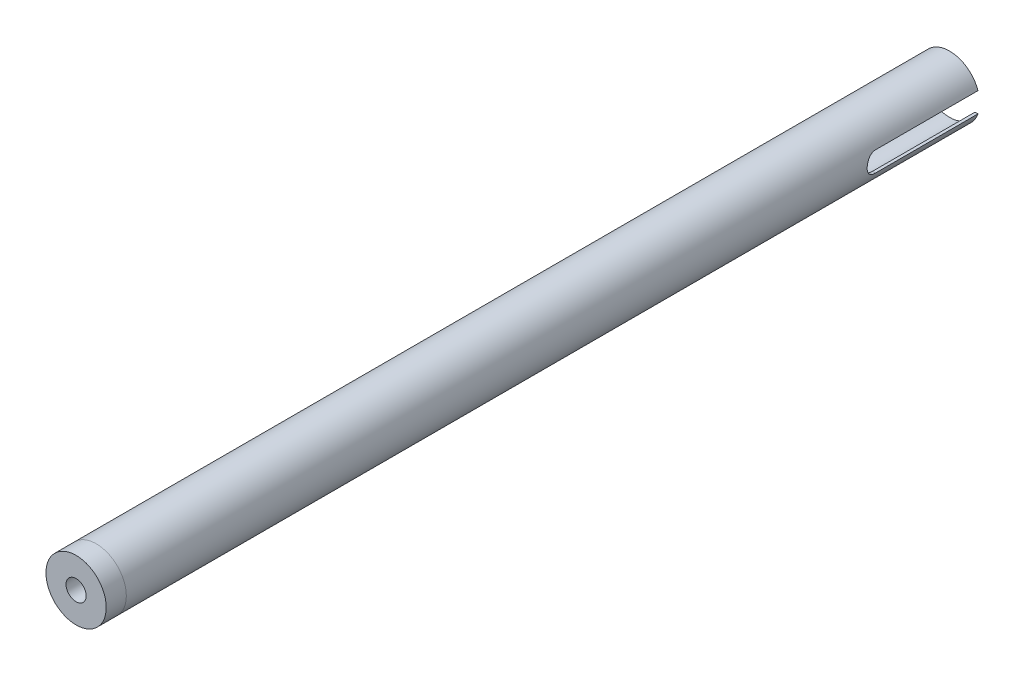
SolidWorks part; units mm, degrees
material "AISI 4130 Steel, annealed at 865C"
ref_plane "Front Plane" through (0, 0, 0) normal (0, 0, 1) x (1, 0, 0)
ref_plane "Top Plane" through (0, 0, 0) normal (0, 1, 0) x (1, 0, 0)
ref_plane "Right Plane" through (0, 0, 0) normal (1, 0, 0) x (0, 0, -1)
sketch "Axis" plane through (0, 0, 0) normal (0, 1, 0) x (1, 0, 0)
  line L0 (0, 0) -> (0, 275.9814) construction
  line L1 (0, 0) -> (0, -21.9075) construction
  line L2 (0, 275.9814) -> (-9.525, 275.9814) construction
  line L3 (0, 301.0104) -> (-10.414, 273.6453) construction
  dimension "D1" = 21.9075
  dimension "D2" = 9.525
sketch "Sketch1" plane through (0, 0, 0) normal (0, 0, 1) x (1, 0, 0)
  line L0 (-9.525, 0) -> (9.525, 0) construction
  line L1 (-8.9803, 3.175) -> (8.9803, 3.175)
  line L2 (-8.9803, -3.175) -> (8.9803, -3.175)
  circle A0 centre (0, 0) radius 9.525
  circle A1 centre (0, 0) radius 8.636
  circle A2 centre (0, 0) radius 3.175
  dimension "D1" = 19.05
  dimension "D3" = 6.35
  dimension "D2" = 0.889
  dimension "D4" = 6.35
extrude "Threaded insert 1-1" add sketch "Sketch1" against normal blind 6.35 contours A2 L1 A1 | A1 L1 A0 | A2 L0 A1 L1 | A1 L0 A0 L1 | L0 A1 L2 A0 | L0 A2 L2 A1 | A2 L2 A1 | A1 L2 A0 | L0 A1 L2 A2 | L0 A0 L2 A1 | A0 L0 A1 L1 | A1 L0 A2 L1 region at (5.4259, 1.6615, 0) region at (5.4259, -1.6615, 0) region at (8.8881, 1.6046, 0) region at (8.8881, -1.6046, 0) region at (-5.4259, -1.6615, 0) region at (-5.4259, 1.6615, 0) region at (0, 5.4321, 0) region at (0, -5.4321, 0) region at (0, 8.8265, 0) region at (8.5057, -3.3655, 0) region at (-8.8881, -1.6046, 0) region at (-8.8881, 1.6046, 0)
extrude "Threaded insert 1-2" add sketch "Sketch1<3>" against normal blind 6.35 from surface contours A2 L1 A1 | A2 L0 A1 L1 | L0 A2 L2 A1 | A2 L2 A1 | L0 A1 L2 A2 | A1 L0 A2 L1 region at (5.4259, 1.6615, 0) region at (5.4259, -1.6615, 0) region at (-5.4259, -1.6615, 0) region at (-5.4259, 1.6615, 0) region at (0, 5.4321, 0) region at (0, -5.4321, 0) starting at face at (9.525, 0, -6.35)
sketch "Sketch1<3>" plane through (0, 0, 0) normal (0, 0, 1) x (1, 0, 0) same geometry as "Sketch1"
extrude "A-arm tube" add sketch "Sketch1<4>" against normal up to vertex (275.9814 mm away) from surface separate body contours A1 L1 A0 | A1 L0 A0 L1 | L0 A1 L2 A0 | A1 L2 A0 | L0 A0 L2 A1 | A0 L0 A1 L1 region at (8.8881, 1.6046, 0) region at (8.8881, -1.6046, 0) region at (0, 8.8265, 0) region at (8.5057, -3.3655, 0) region at (-8.8881, -1.6046, 0) region at (-8.8881, 1.6046, 0) up to point (0, 0, -275.9814) starting at face at (8.636, 0, -6.35)
sketch "Sketch1<4>" plane through (0, 0, 0) normal (0, 0, 1) x (1, 0, 0) same geometry as "Sketch1"
extrude "Apex slot" cut sketch "Sketch1<5>" along normal blind 35.56 from surface contours A0 L0 A1 L1 | L0 A0 L2 A1 | A1 L0 A0 L1 | L0 A1 L2 A0 region at (8.8881, 1.6046, 0) region at (8.8881, -1.6046, 0) region at (-8.8881, -1.6046, 0) region at (-8.8881, 1.6046, 0) starting at face at (8.636, 0, -275.9814)
sketch "Sketch1<5>" plane through (0, 0, 0) normal (0, 0, 1) x (1, 0, 0) same geometry as "Sketch1"
fillet "Fillet1" radius 3.175 4 edges at (-8.5057, 3.175, -240.4214) (-8.5057, -3.175, -240.4214) (8.5057, -3.175, -240.4214) (8.5057, 3.175, -240.4214)
equation "\"tube diameter\"= 3 / 4"
equation "\"tube thickness\"= .035"
equation "\"apex thickness\"= .25"
equation "\"tube slot\"= 1.4"
equation "\"D1@Sketch1\"=\"tube diameter\""
equation "\"D2@Sketch1\"=\"tube thickness\""
equation "\"threaded insert hole\"= 1 / 4"
equation "\"D3@Sketch1\"=\"threaded insert hole\""
equation "\"D4@Sketch1\"=\"apex thickness\""
equation "\"D1@Apex slot\" = \"tube slot\""
equation "\"D1@Fillet1\"=\"apex thickness\"/2"
equation "\"D2@Axis\"=\"tube diameter\"/2"
